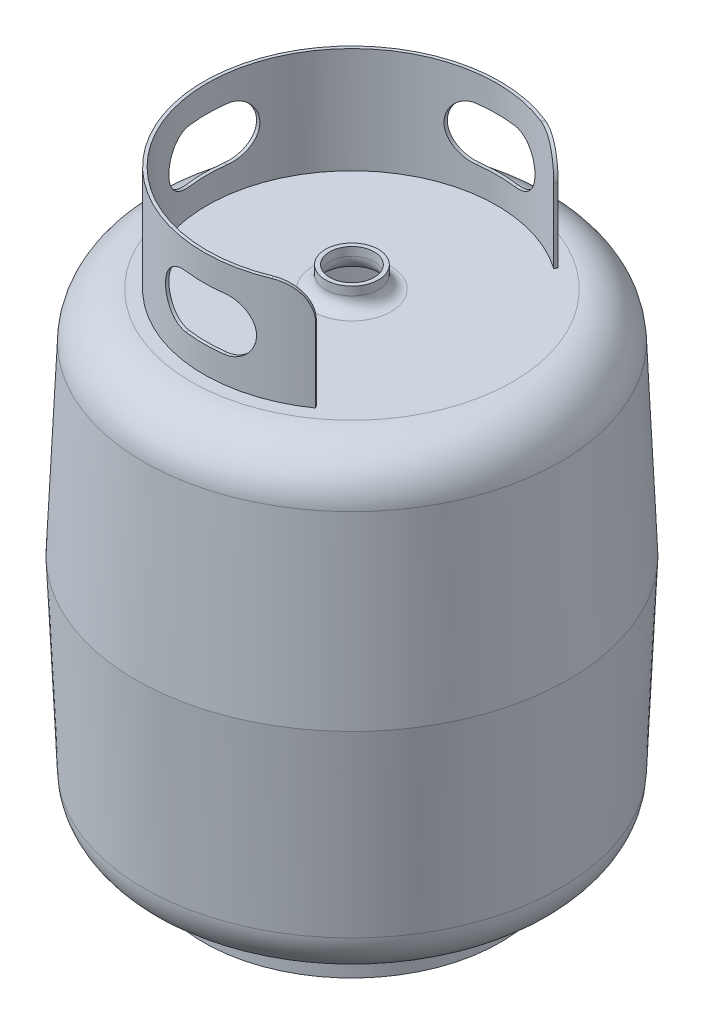
SolidWorks part; units mm, degrees
material "Alliage 1060"
ref_plane "Plan de face" through (0, 0, 0) normal (0, 0, 1) x (1, 0, 0)
ref_plane "Plan de dessus" through (0, 0, 0) normal (0, 1, 0) x (1, 0, 0)
ref_plane "Plan de droite" through (0, 0, 0) normal (1, 0, 0) x (0, 0, -1)
sketch "Esquisse1" plane through (0, 0, 0) normal (0, 0, 1) x (1, 0, 0)
  line L0 (0, 0) -> (0, 717.3714) construction
  line L1 (0, 0) -> (151.9219, 0)
  line L2 (196.879, 43.0371) -> (204.4963, 217.5)
  line L3 (204.4963, 217.5) -> (196.879, 391.9629)
  line L4 (151.9219, 435) -> (37, 435)
  line L5 (25, 447) -> (25, 455)
  line L6 (0, 4) -> (151.9219, 4)
  line L7 (192.8828, 43.2116) -> (200.4924, 217.5)
  line L8 (200.4924, 217.5) -> (192.8828, 391.7884)
  line L9 (151.9219, 431) -> (37, 431)
  line L10 (21, 447) -> (21, 455)
  line L11 (21, 455) -> (25, 455)
  line L12 (0, 4) -> (0, 0)
  arc A0 (37, 435) -> (25, 447) centre (37, 447) cw
  arc A1 (196.879, 43.0371) -> (151.9219, 0) centre (151.9219, 45) cw
  arc A2 (196.879, 391.9629) -> (151.9219, 435) centre (151.9219, 390) ccw
  arc A3 (192.8828, 43.2116) -> (151.9219, 4) centre (151.9219, 45) cw
  arc A4 (192.8828, 391.7884) -> (151.9219, 431) centre (151.9219, 390) ccw
  arc A5 (37, 431) -> (21, 447) centre (37, 447) cw
  point P14 (195, 0)
  point P17 (195, 435)
  dimension "D3" = 45
  dimension "D6" = 12
  dimension "D1" = 435
  dimension "D2" = 92.5
  dimension "D4" = 92.5
  dimension "D5" = 390
  dimension "D7" = 25
  dimension "D8" = 20
  dimension "D9" = 4
revolve "Révolution2" add sketch "Esquisse1" angle 360 about L0
sketch "Esquisse2" plane through (0, 0, 0) normal (0, -1, 0) x (1, 0, 0)
  circle A0 centre (0, 0) radius 139.9219
  circle A1 centre (0, 0) radius 151.9219 construction
  circle A2 centre (0, 0) radius 136.9219
  dimension "D1" = 12
  dimension "D2" = 3
extrude "Boss.-Extru.1" add sketch "Esquisse2" along normal blind 30
sketch "Esquisse3" plane through (0, 435, 0) normal (0, 1, 0) x (1, 0, 0)
  line L0 (0, 0) -> (272.5441, 0) construction
  line L1 (0, 0) -> (151.0873, 215.775)
  line L2 (0, 0) -> (173.7897, -248.1974)
  circle A0 centre (0, 0) radius 139.9219
  circle A1 centre (0, 0) radius 151.9219 construction
  circle A2 centre (0, 0) radius 136.9219
  dimension "D1" = 12
  dimension "D3" = 55
  dimension "D4" = 55
  dimension "D2" = 3
extrude "Boss.-Extru.2" add sketch "Esquisse3" along normal blind 100 contours A2 L1 A0 L2 region at (-137.2779, 435, 0)
fillet "Congé1" radius 30 2 edges at (79.3955, 535, 113.3886) (79.3955, 535, -113.3886)
sketch "Esquisse6" plane through (0, 0, 0) normal (0, 0, 1) x (1, 0, 0)
  line L0 (18, 485) -> (-18, 485) construction
  line L1 (18, 460) -> (-18, 460)
  line L2 (18, 510) -> (-18, 510)
  line L3 (52.0523, 535) -> (-136.9219, 535) construction
  arc A0 (18, 460) -> (18, 510) centre (18, 485) ccw
  arc A1 (-18, 510) -> (-18, 460) centre (-18, 485) ccw
  point P2 (0, 485)
  dimension "D1" = 36
  dimension "D2" = 50
  dimension "D3" = 50
extrude "Enlèv. mat.-Extru.1" cut sketch "Esquisse6" along normal through all
pattern_circular "Répétition circulaire1" count 3 over 180 about axis through (0, 535, 0) along (0, -1, 0) of "Enlèv. mat.-Extru.1"
equation "\"A\"= 390"
equation "\"B\"= 435"
equation "\"D1@Esquisse1\"=\"B\""
equation "\"D5@Esquisse1\"=\"A\""
